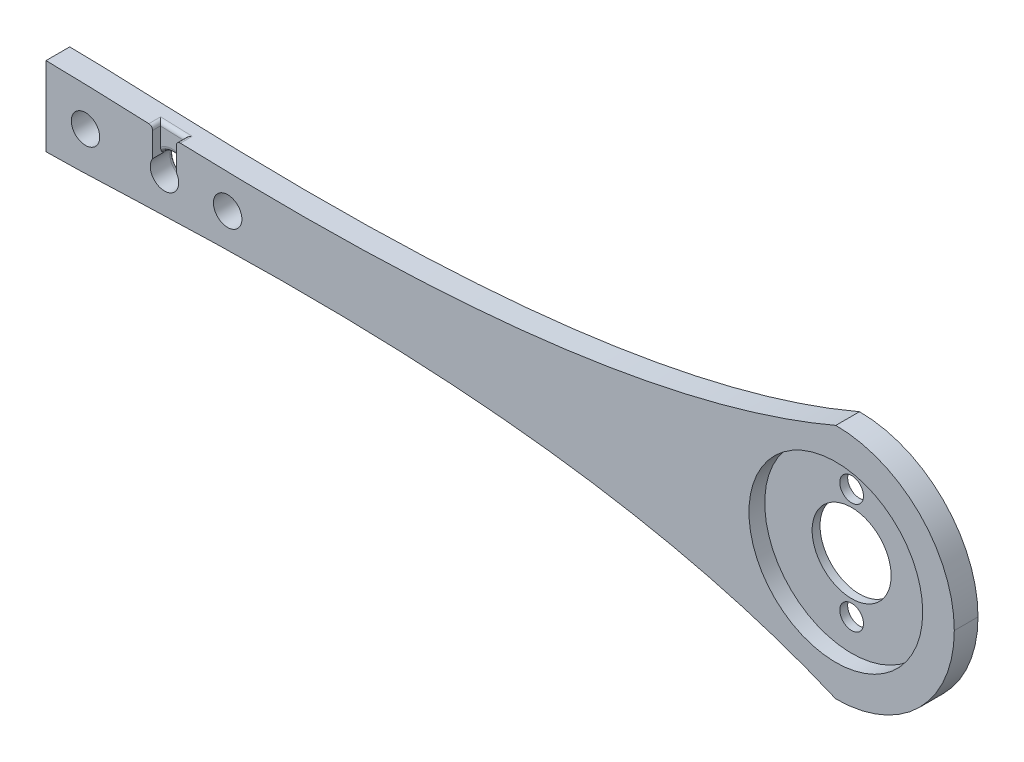
SolidWorks part; units mm, degrees
ref_plane "Plan de face" through (0, 0, 0) normal (0, 0, 1) x (1, 0, 0)
ref_plane "Plan de dessus" through (0, 0, 0) normal (0, 1, 0) x (1, 0, 0)
ref_plane "Plan de droite" through (0, 0, 0) normal (1, 0, 0) x (0, 0, -1)
sketch "Esquisse1" plane through (0, 0, 0) normal (0, 0, 1) x (1, 0, 0)
  line L0 (0, 0) -> (-100, 11.7647)
  line L1 (0, 0) -> (0, 33.5294)
  line L2 (-100, 11.7647) -> (-100, 21.7647)
  line L3 (0, 33.5294) -> (-100, 21.7647)
  line L16 (-15, 16.7647) -> (-15, 31.7647) construction
  line L17 (-15, 31.7647) -> (-15, 16.7647) construction
  line L18 (-15, 16.7647) -> (0, 16.7647) construction
  line L19 (0, 16.7647) -> (-15, 16.7647) construction
  line L20 (-15, 16.7647) -> (-15, 1.7647) construction
  line L21 (-100, 16.7647) -> (0, 16.7647) construction
  line L22 (-100, 21.7647) -> (-100, 11.7647)
  line L23 (-100, 21.7647) -> (-115, 21.7647)
  line L24 (-100, 11.7647) -> (-115, 11.7647)
  line L25 (-115, 21.7647) -> (-115, 11.7647)
  line L26 (-115, 21.7647) -> (-100, 21.7647) construction
  line L27 (-100, 21.7647) -> (-50, 16.7647) construction
  line L28 (-50, 16.7647) -> (-15, 31.7647) construction
  line L29 (-115, 11.7647) -> (-100, 11.7647) construction
  line L30 (-100, 11.7647) -> (-50, 16.7647) construction
  line L31 (-50, 16.7647) -> (-15, 1.7647) construction
  circle A0 centre (-15, 16.7647) radius 5
  circle A1 centre (-15, 16.7647) radius 12.5
  circle A2 centre (-15, 23.7647) radius 1.5
  circle A3 centre (-15, 9.7647) radius 1.5
  circle A4 centre (-110, 16.7647) radius 1.8
  circle A5 centre (-100, 16.7647) radius 1.8
  circle A6 centre (-92, 16.7647) radius 1.8
  spline S0 degree 3 poles (-115, 21.7647) (-100, 21.7647) (-50, 16.7647) (-15, 31.7647) knots 0 0 0 0 1 1 1 1
  spline S1 degree 3 poles (-115, 11.7647) (-100, 11.7647) (-50, 16.7647) (-15, 1.7647) knots 0 0 0 0 1 1 1 1
  point P13 (-50, 16.7647)
  dimension "D3" = 10
  dimension "D16" = 5
  dimension "D1" = 25
  dimension "D7" = 14
  dimension "D9" = 3
  dimension "D10" = 3
  dimension "D12" = 3.6
  dimension "D13" = 3.6
  dimension "D18" = 3.6
  dimension "D2" = 10
  dimension "D4" = 100
  dimension "D5" = 15
  dimension "D6" = 15
  dimension "D8" = 7
  dimension "D11" = 10
  dimension "D14" = 5
  dimension "D15" = 5
  dimension "D17" = 18
extrude "Boss.-Extru.1" add sketch "Esquisse1" along normal blind 3 contours L0 | L3 | L22 S1 L0 L1 L3 S0 A1 | L25 S1 L22 S0 | A1 | A0 | A3 | A2 region at (-44.1741, 16.7647, 0) region at (-107.7198, 16.7647, 0)
fillet "Congé1" radius 15 2 edges at (0, 33.5294, 1.5) (0, 0, 1.5)
sketch "Esquisse2" plane through (0, 0, 3) normal (0, 0, 1) x (1, 0, 0)
  line L0 (-15, 31.7647) -> (-15, 1.7647)
  circle A0 centre (-15, 16.7647) radius 11
  arc A1 (-15, 31.7647) -> (-15, 1.7647) centre (-15, 16.7647) cw
  spline S0 degree 3 poles (-115, 11.7647) (-100, 11.7647) (-50, 16.7647) (-15, 1.7647) knots 0 0 0 0 1 1 1 1 construction
  circle M7 centre (-15, 16.7647) radius 5
  circle M11 centre (-15, 9.7647) radius 1.5
  circle M12 centre (-15, 23.7647) radius 1.5
  dimension "D1" = 22
extrude "Enlèv. mat.-Extru.1" cut sketch "Esquisse2" against normal blind 2 contours L0 A0 M11 M7 M12 | L0 A0 M12 M7 M11 region at (-9.4374, 16.7647, 3) region at (-20.5626, 16.7647, 3)
sketch "Esquisse3" plane through (0, 0, 3) normal (0, 0, 1) x (1, 0, 0)
  line L0 (-101.5, 21.339) -> (-98.5, 21.339)
  line L1 (-101.5, 21.339) -> (-101.5, 16.7647)
  line L2 (-98.5, 21.339) -> (-98.5, 16.7647)
  line L3 (-101.5, 16.7647) -> (-98.5, 16.7647)
  line L5 (-111.8, 16.7647) -> (-98.2, 16.7647) construction
  circle A0 centre (-110, 16.7647) radius 1.8 construction
  circle A1 centre (-100, 16.7647) radius 1.8 construction
  spline S0 degree 3 poles (-115, 21.7647) (-100, 21.7647) (-50, 16.7647) (-15, 31.7647) knots 0 0 0 0 1 1 1 1 construction
  dimension "D1" = 8.5
  dimension "D2" = 3
extrude "Enlèv. mat.-Extru.2" cut sketch "Esquisse3" against normal blind 1
fillet "Congé2" radius 0.5 5 edges at (-98.5, 21.235, 2.5) (-101.5, 21.339, 2.5) (-100, 18.5647, 2) (-98.2, 16.7647, 0)
